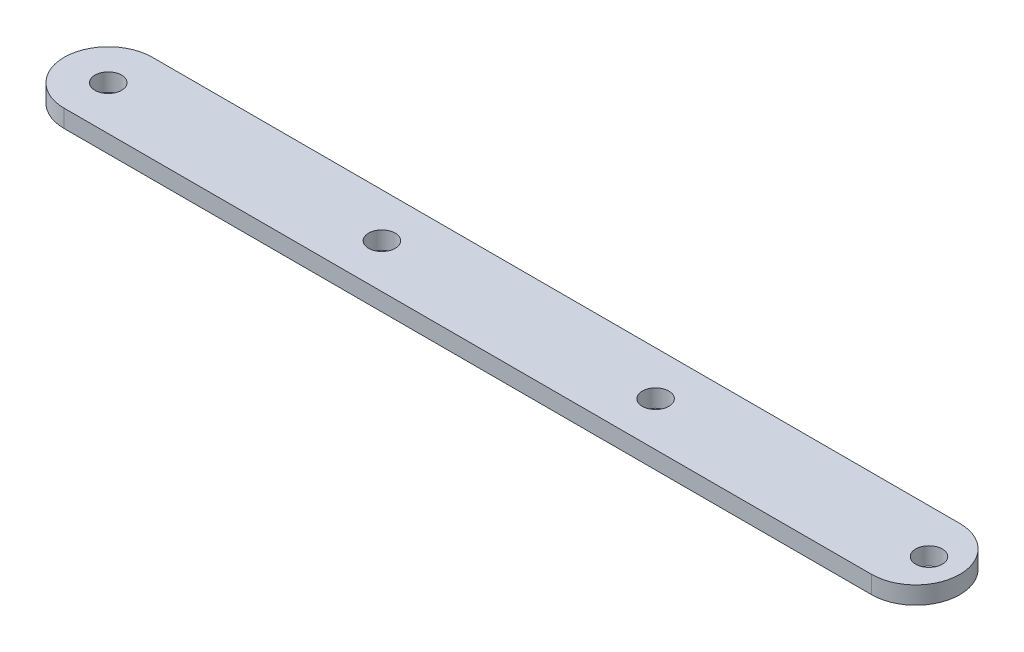
SolidWorks part; units mm, degrees
ref_plane "Front Plane" through (0, 0, 0) normal (0, 0, 1) x (1, 0, 0)
ref_plane "Top Plane" through (0, 0, 0) normal (0, 1, 0) x (1, 0, 0)
ref_plane "Right Plane" through (0, 0, 0) normal (1, 0, 0) x (0, 0, -1)
sketch "Sketch1" plane through (0, 0, 0) normal (0, 1, 0) x (1, 0, 0)
  line L0 (-124.1, 0) -> (58.99, 0) construction
  line L1 (-124.1, 0) -> (58.99, 0) construction
  line L2 (-124.1, 10) -> (58.99, 10)
  line L3 (-124.1, -10) -> (58.99, -10)
  arc A0 (-124.1, 10) -> (-124.1, -10) centre (-124.1, 0) ccw
  arc A1 (58.99, -10) -> (58.99, 10) centre (58.99, 0) ccw
  circle A3 centre (-124.1, 0) radius 3.01
  circle A4 centre (-62.05, 0) radius 3.01
  circle A5 centre (0, 0) radius 3.01
  circle A6 centre (62, 0) radius 3.01
  point P3 (-124.1, 0)
  point P4 (-62.05, 0)
  point P5 (62, 0)
  point P6 (-32.555, 0)
  point P11 (-186.4, 0)
  point P12 (-145.8095, 0)
  point P21 (58.99, 0)
  point P22 (0, 0)
  point P23 (0, 0)
  point P24 (-124.1, 0)
  dimension "D6" = 20
  dimension "D2" = 62.05
  dimension "D3" = 62.05
  dimension "D4" = 62
extrude "Boss-Extrude1" add sketch "Sketch1" along normal blind 4
